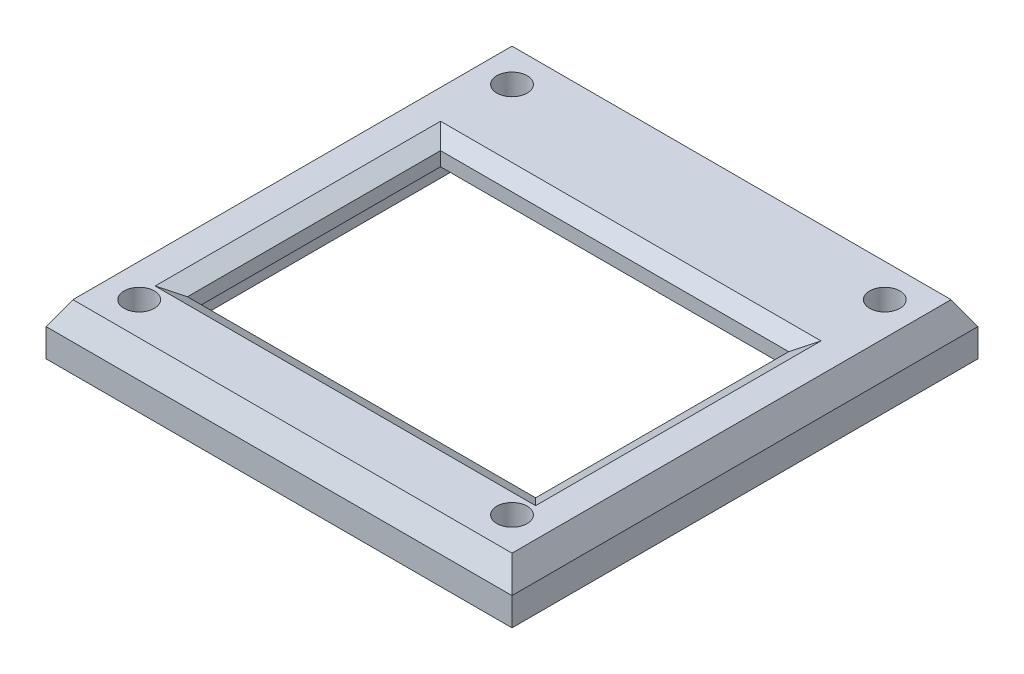
SolidWorks part; units mm, degrees
ref_plane "Front Plane" through (0, 0, 0) normal (0, 0, 1) x (1, 0, 0)
ref_plane "Top Plane" through (0, 0, 0) normal (0, 1, 0) x (1, 0, 0)
ref_plane "Right Plane" through (0, 0, 0) normal (1, 0, 0) x (0, 0, -1)
sketch "Sketch1" plane through (0, 0, 0) normal (0, 1, 0) x (1, 0, 0)
  line L0 (0, 23) -> (0, -23) construction
  line L1 (-23, 23) -> (23, 23)
  line L2 (-23, 23) -> (-23, -23)
  line L3 (-23, -23) -> (23, -23)
  line L4 (23, 23) -> (23, -23)
  line L5 (-23, 23) -> (23, -23) construction
  line L6 (-23, -23) -> (23, 23) construction
  line L7 (-25, 25) -> (25, 25)
  line L8 (-25, 25) -> (-25, -25)
  line L9 (-25, -25) -> (25, -25)
  line L10 (25, 25) -> (25, -25)
  line L11 (-25, 25) -> (25, -25) construction
  line L12 (-25, -25) -> (25, 25) construction
  line L13 (18.6813, -16.1456) -> (-18.6813, -16.1456)
  line L14 (-20.625, 17.475) -> (20.625, 17.475)
  line L15 (-20.625, 17.475) -> (-20.625, -16.775)
  line L16 (-20.625, -16.775) -> (20.625, -16.775)
  line L17 (20.625, 17.475) -> (20.625, -16.775)
  line L18 (-20.625, 17.475) -> (20.625, -16.775) construction
  line L19 (-20.625, -16.775) -> (20.625, 17.475) construction
  line L24 (18.6813, -16.1456) -> (18.6813, 11.0121)
  line L25 (18.6813, 11.0121) -> (-18.6813, 11.0121)
  line L26 (-18.6813, 11.0121) -> (-18.6813, -16.1456)
  circle A0 centre (-20, 20) radius 1.625
  circle A1 centre (20, 20) radius 1.625
  circle A2 centre (20, -20) radius 1.625
  circle A3 centre (-20, -20) radius 1.625
  point P0 (0, 0)
  point P8 (0, 0)
  point P17 (0, 0)
  point P22 (0, 0.35)
  point P29 (0, -16.1456)
  point P32 (-18.6762, 11.0121)
  point P33 (18.6813, -16.1456)
  dimension "D1" = 3.25
  dimension "D3" = 50
  dimension "D4" = 46
  dimension "D5" = 41.25
  dimension "D6" = 34.25
  dimension "D7" = 40
  dimension "D8" = 0.35
  dimension "D2" = 4
extrude "Boss-Extrude1" add sketch "Sketch1" along normal blind 3 contours L10 L7 L8 L9 L1 L4 L3 L2 | L4 L1 L2 L3 A3 A2 A1 A0 L14 L17 L16 L15 region at (0, 0, -22.3495) region at (0, 0, -24.2929)
extrude "Boss-Extrude2" add sketch "Sketch1<3>" along normal blind 2.5 from offset 3 contours L17 L14 L15 L16 L26 L25 L24 L13 | L4 L1 L2 L3 A3 A2 A1 A0 L14 L17 L16 L15 region at (0, 0, -22.3495) region at (0, 0, -16.9388)
sketch "Sketch1<3>" plane through (0, 0, 0) normal (0, 1, 0) x (1, 0, 0) same geometry as "Sketch1"
chamfer "Chamfer1" distance 2 angle 60 4 edges at (0, 3, -23) (-23, 3, 0) (0, 3, 23) (23, 3, 0) first distance on face at (0, 3, 0)
chamfer "Chamfer2" distance 1 angle 60 4 edges at (-18.6813, 5.5, 2.5668) (0, 5.5, -11.0121) (18.6813, 5.5, 2.5668) (0, 5.5, 16.1456) first distance on face at (-18.6813, 4.25, 2.5668) first distance on face at (0, 4.25, -11.0121) first distance on face at (18.6813, 4.25, 2.5668) first distance on face at (0, 4.25, 16.1456)
